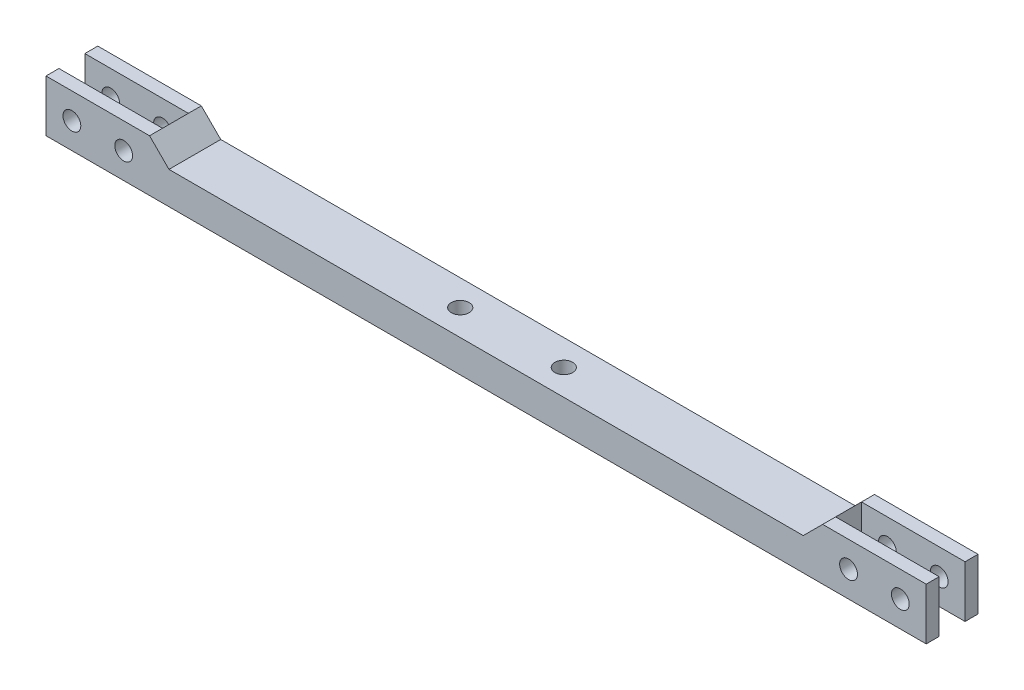
SolidWorks part; units mm, degrees
ref_plane "Front Plane" through (0, 0, 0) normal (0, 0, 1) x (1, 0, 0)
ref_plane "Top Plane" through (0, 0, 0) normal (0, 1, 0) x (1, 0, 0)
ref_plane "Right Plane" through (0, 0, 0) normal (1, 0, 0) x (0, 0, -1)
sketch "Sketch1" plane through (0, 0, 0) normal (0, 1, 0) x (1, 0, 0)
  line L0 (-107.95, 0) -> (107.95, 0)
  line L1 (107.95, 0) -> (107.95, 3.175)
  line L2 (107.95, 3.175) -> (82.55, 3.175)
  line L3 (82.55, 3.175) -> (82.55, 9.525)
  line L4 (82.55, 9.525) -> (107.95, 9.525)
  line L5 (107.95, 9.525) -> (107.95, 12.7)
  line L6 (107.95, 12.7) -> (-107.95, 12.7)
  line L7 (-107.95, 12.7) -> (-107.95, 9.525)
  line L8 (-107.95, 9.525) -> (-82.55, 9.525)
  line L9 (-82.55, 9.525) -> (-82.55, 3.175)
  line L10 (-82.55, 3.175) -> (-107.95, 3.175)
  line L11 (-107.95, 3.175) -> (-107.95, 0)
  point P4 (0, 0)
  dimension "D1" = 215.9
  dimension "D2" = 12.7
  dimension "D3" = 3.175
  dimension "D4" = 3.175
  dimension "D5" = 25.4
  dimension "D6" = 25.4
extrude "Boss-Extrude1" add sketch "Sketch1" along normal mid plane 12.7
sketch "Sketch2" plane through (0, 0, 0) normal (0, 0, 1) x (1, 0, 0)
  line L0 (-107.95, 6.35) -> (-107.95, -6.35) construction
  line L1 (107.95, 6.35) -> (107.95, -6.35) construction
  circle A0 centre (-101.6, 0) radius 2.1828
  circle A1 centre (-88.9, 0) radius 2.1828
  circle A2 centre (101.6, 0) radius 2.1828
  circle A3 centre (88.9, 0) radius 2.1828
  dimension "D5" = 4.3656
  dimension "D6" = 4.3656
  dimension "D7" = 4.3656
  dimension "D8" = 4.3656
  dimension "D1" = 6.35
  dimension "D2" = 12.7
  dimension "D3" = 6.35
  dimension "D4" = 12.7
extrude "Cut-Extrude1" cut sketch "Sketch2" against normal through all both and the other way through all
sketch "Sketch3" plane through (0, 0, 0) normal (0, 0, 1) x (1, 0, 0)
  line L0 (-82.55, 6.35) -> (-77.7875, 1.5875)
  line L1 (-107.95, 6.35) -> (107.95, 6.35) construction
  line L2 (-77.7875, 1.5875) -> (77.7875, 1.5875)
  line L3 (77.7875, 1.5875) -> (82.55, 6.35)
  line L4 (-107.95, 6.35) -> (-107.95, -6.35) construction
  line L5 (107.95, 6.35) -> (107.95, -6.35) construction
  line L6 (-82.55, 6.35) -> (82.55, 6.35)
  dimension "D1" = 25.4
  dimension "D2" = 25.4
  dimension "D3" = 4.7625
  dimension "D4" = 45
  dimension "D5" = 45
extrude "Cut-Extrude2" cut sketch "Sketch3" against normal through all both and the other way through all
sketch "Sketch4" plane through (0, -6.35, 0) normal (0, -1, 0) x (1, 0, 0)
  circle A0 centre (-12.7, -6.35) radius 2.1828
  circle A1 centre (12.7, -6.35) radius 2.1828
  point P4 (0, 0)
  dimension "D4" = 4.3656
  dimension "D5" = 4.3656
  dimension "D1" = 12.7
  dimension "D2" = 12.7
  dimension "D3" = 6.35
extrude "Cut-Extrude3" cut sketch "Sketch4" against normal through all both and the other way through all
